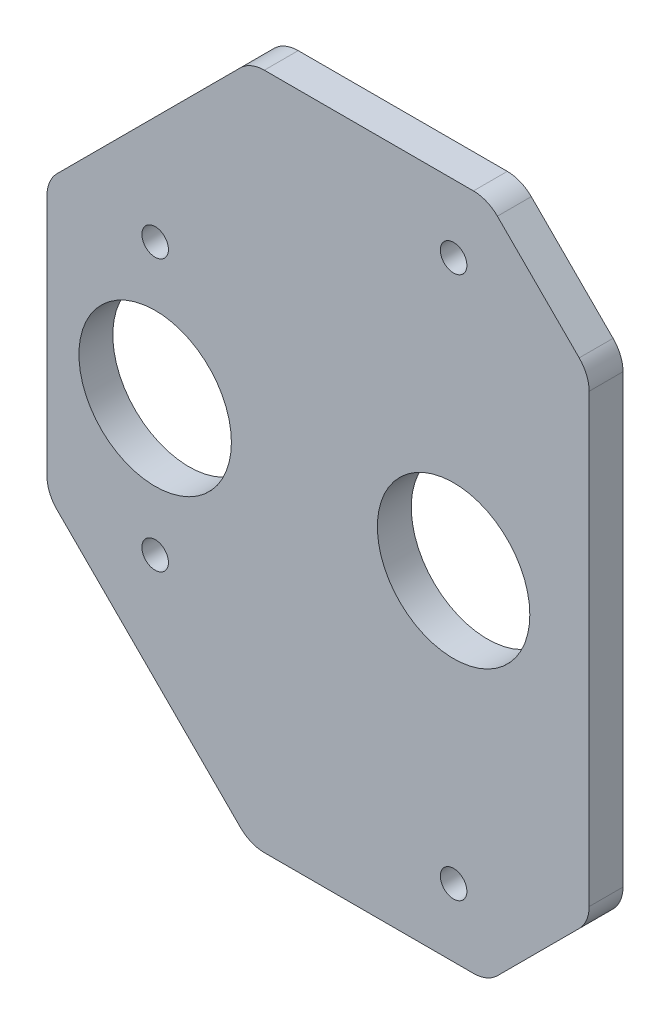
SolidWorks part; units mm, degrees
ref_plane "Front Plane" through (0, 0, 0) normal (0, 0, 1) x (1, 0, 0)
ref_plane "Top Plane" through (0, 0, 0) normal (0, 1, 0) x (1, 0, 0)
ref_plane "Right Plane" through (0, 0, 0) normal (1, 0, 0) x (0, 0, -1)
sketch "Sketch1" plane through (0, 0, 0) normal (0, 0, 1) x (1, 0, 0)
  line L1 (0, 0) -> (101.6, 0)
  line L2 (0, 0) -> (0, 127)
  line L3 (0, 127) -> (101.6, 127)
  line L4 (101.6, 0) -> (101.6, 127)
  circle A0 centre (20.2692, 88.9) radius 2.4892
  circle A1 centre (20.2692, 63.5) radius 14.2875
  circle A2 centre (20.2692, 38.1) radius 2.4892
  circle A3 centre (76.2, 114.3) radius 2.4892
  circle A4 centre (76.2, 63.5) radius 14.2875
  circle A5 centre (76.2, 12.7) radius 2.4892
  dimension "D3" = 25.4
  dimension "D10" = 25.4
  dimension "D12" = 4.9784
  dimension "D13" = 4.9784
  dimension "D14" = 28.575
  dimension "D15" = 28.575
  dimension "D16" = 4.9784
  dimension "D17" = 4.9784
  dimension "D2" = 101.6
  dimension "D4" = 63.5
  dimension "D5" = 50.8
  dimension "D6" = 50.8
  dimension "D7" = 12.7
  dimension "D8" = 25.4
  dimension "D9" = 25.4
  dimension "D11" = 127
  dimension "D18" = 55.9308
extrude "Boss-Extrude1" add sketch "Sketch1" along normal mid plane 6.35
chamfer "Chamfer2" distance 38.1 angle 45 2 edges at (0, 0, 0) (0, 127, 0)
chamfer "Chamfer3" distance 19.05 angle 45 2 edges at (101.6, 0, 0) (101.6, 127, 0)
fillet "Fillet2" radius 6.35 8 edges at (101.6, 107.95, 0) (82.55, 127, 0) (0, 88.9, 0) (0, 38.1, 0) (38.1, 0, 0) (82.55, 0, 0) (101.6, 19.05, 0) (38.1, 127, 0)
sketch "Sketch2" [suppressed] plane through (0, 0, 3.175) normal (0, 0, 1) x (1, 0, 0)
  line L0 (47.9143, 84.7951) -> (26.5569, 106.1525)
  line L1 (48.8442, 82.55) -> (48.8442, 117.6022)
  line L2 (45.6692, 60.325) -> (101.6, 60.325)
  line L3 (45.6692, 60.325) -> (6.35, 60.325)
  line L4 (48.8442, 31.75) -> (48.8442, 82.55)
  line L5 (42.4942, 31.75) -> (42.4942, 6.35)
  line L6 (43.4241, 33.9951) -> (20.6603, 11.2312)
  line L7 (43.4241, 80.3049) -> (22.0667, 101.6623)
  line L8 (45.6692, 31.75) -> (45.6692, 82.55) construction
  line L9 (45.6692, 57.15) -> (101.6, 57.15) construction
  line L10 (101.6, 57.15) -> (120.65, 57.15) construction
  line L11 (45.6692, 82.55) -> (24.3118, 103.9074) construction
  line L12 (45.6692, 57.15) -> (6.35, 57.15) construction
  line L13 (45.6692, 31.75) -> (22.9054, 8.9862) construction
  line L14 (45.6692, 31.75) -> (45.6692, 6.35) construction
  line L15 (45.6692, 82.55) -> (45.6692, 117.6022) construction
  line L16 (95.25, 21.6803) -> (95.25, 105.3197)
  line L17 (95.25, 105.3197) -> (79.9197, 120.65)
  line L18 (79.9197, 120.65) -> (40.7303, 120.65)
  line L19 (40.7303, 120.65) -> (6.35, 86.2697)
  line L20 (6.35, 86.2697) -> (6.35, 40.7303)
  line L21 (6.35, 40.7303) -> (40.7303, 6.35)
  line L22 (40.7303, 6.35) -> (79.9197, 6.35)
  line L23 (79.9197, 6.35) -> (95.25, 21.6803)
  line L24 (95.25, 21.6803) -> (95.25, 105.3197)
  line L25 (95.25, 105.3197) -> (79.9197, 120.65)
  line L26 (79.9197, 120.65) -> (40.7303, 120.65)
  line L27 (40.7303, 120.65) -> (6.35, 86.2697)
  line L28 (6.35, 86.2697) -> (6.35, 40.7303)
  line L29 (6.35, 40.7303) -> (40.7303, 6.35)
  line L30 (40.7303, 6.35) -> (79.9197, 6.35)
  line L31 (79.9197, 6.35) -> (95.25, 21.6803)
  line L32 (42.4942, 82.55) -> (42.4942, 117.6022)
  line L33 (45.6692, 53.975) -> (101.6, 53.975)
  line L34 (45.6692, 53.975) -> (6.35, 53.975)
  line L35 (42.4942, 31.75) -> (42.4942, 82.55)
  line L36 (48.8442, 31.75) -> (48.8442, 6.35)
  line L37 (47.9143, 29.5049) -> (25.1504, 6.7411)
  line L38 (101.6, 53.975) -> (120.65, 53.975)
  line L39 (101.6, 60.325) -> (120.65, 60.325)
  circle A11 centre (45.6692, 57.15) radius 17.4625
  circle A12 centre (45.6692, 82.55) radius 6.35
  circle A13 centre (101.6, 57.15) radius 17.4625
  circle A14 centre (101.6, 107.95) radius 6.35
  circle A15 centre (101.6, 6.35) radius 6.35
  circle A16 centre (45.6692, 31.75) radius 6.35
  circle A17 centre (20.2692, 69.85) radius 14.2875 construction
  circle A18 centre (76.2, 69.85) radius 14.2875 construction
  dimension "D2" = 12.7
  dimension "D3" = 3.3519
  dimension "D4" = 3.3519
  dimension "D1" = 6.35
  dimension "D5" = 3.175
  dimension "D6" = 3.175
  dimension "D7" = 3.175
  dimension "D8" = 3.175
